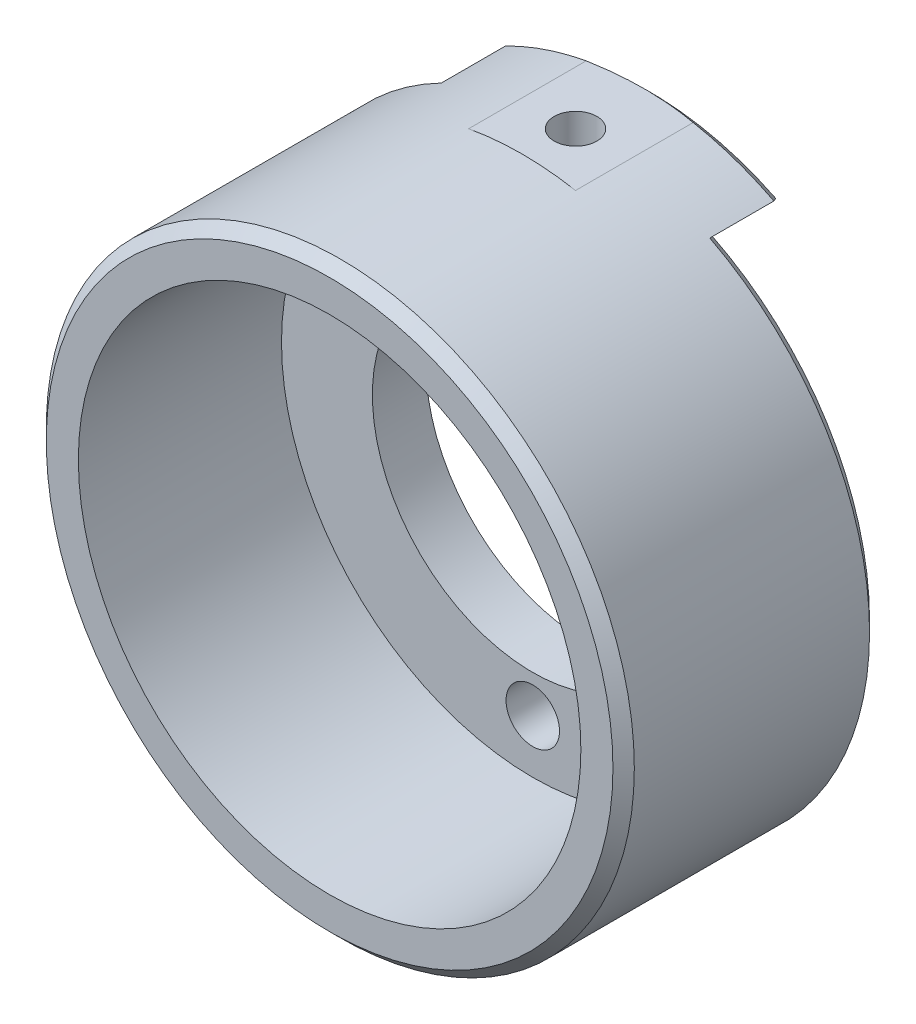
SolidWorks part; units mm, degrees
ref_plane "Front Plane" through (0, 0, 0) normal (0, 0, 1) x (1, 0, 0)
ref_plane "Top Plane" through (0, 0, 0) normal (0, 1, 0) x (1, 0, 0)
ref_plane "Right Plane" through (0, 0, 0) normal (1, 0, 0) x (0, 0, -1)
sketch "Sketch1" plane through (0, 0, 0) normal (0, 1, 0) x (1, 0, 0)
  line L0 (0, -8.6957) -> (0, 15.3043) construction
  line L1 (-15, 24) -> (-23.5, 24)
  line L2 (-15, 24) -> (-15, 19)
  line L3 (-15, 19) -> (-23.5, 19)
  line L4 (-23.5, 24) -> (-23.5, 19)
  line L5 (-23.5, 24) -> (-27.5, 24)
  line L6 (-23.5, 24) -> (-23.5, 0)
  line L7 (-23.5, 0) -> (-27.5, 0)
  line L8 (-27.5, 24) -> (-27.5, 0)
  point P9 (0, 0)
  dimension "D1" = 24
  dimension "D2" = 19
  dimension "D3" = 15
  dimension "D4" = 27.5
  dimension "D5" = 23.5
revolve "Revolve1" add sketch "Sketch1" angle 360 about L0
sketch "Sketch2" plane through (0, 0, -24) normal (0, 0, -1) x (-1, 0, 0)
  line L0 (-2.2498, -15.8188) -> (-12.5556, -24.4665)
  line L1 (2.2498, -15.8188) -> (12.5556, -24.4665)
  line L2 (0, 0) -> (0, -33.4379) construction
  line L3 (0, 0) -> (7.8156, 0) construction
  line L4 (2.2498, 15.8188) -> (12.5556, 24.4665)
  line L5 (-2.2498, 15.8188) -> (-12.5556, 24.4665)
  circle A0 centre (0, -18.5) radius 3.5
  circle A1 centre (0, -18.5) radius 2.5
  circle A2 centre (0, 0) radius 27.5 construction
  circle A3 centre (0, 0) radius 15 construction
  circle A4 centre (0, 18.5) radius 2.5
  circle A5 centre (0, 18.5) radius 3.5
  arc A6 (-12.5556, -24.4665) -> (12.5556, -24.4665) centre (0, 0) ccw
  circle A7 centre (0, 0) radius 27.5
  arc A8 (12.5556, 24.4665) -> (-12.5556, 24.4665) centre (0, 0) ccw
  circle M4 centre (0, 0) radius 27.5
  dimension "D1" = 5
  dimension "D2" = 100
  dimension "D3" = 37
  dimension "D4" = 0
extrude "Boss-Extrude1" add sketch "Sketch2" along normal blind 6 contours L5 A5 L4 M4 | A5 A4 | A0 A1 | A0 L0 L1 M4 region at (0, -23.3823, -24) region at (0, -15.099, -24) region at (0, 23.3823, -24) region at (1.4373, 21.5824, -24)
chamfer "Chamfer1" distance 1 angle 45 5 edges at (27.5, 0, 0) (-27.5, 0, -24) (0, -27.5, -30) (27.5, 0, -24) (0, 27.5, -30)
ref_plane "Plane1" through (0, 30, 0) normal (0, 1, 0) x (1, 0, 0)
sketch "Sketch5" plane through (0, 0, -30) normal (0, 0, -1) x (-1, 0, 0)
  line L0 (5, 27.0416) -> (-5, 27.0416)
  line L1 (0, 0) -> (0, 27.0416) construction
  circle A1 centre (0, 0) radius 27.5
  arc A2 (12.5556, 24.4665) -> (-12.5556, 24.4665) centre (0, 0) ccw construction
  point P3 (0, 25.2007)
  point P7 (0, 0)
  point P11 (0, 0)
  dimension "D1" = 10
sketch "Sketch4" plane through (0, 30, 0) normal (0, 1, 0) x (1, 0, 0)
  line L0 (-5, 30) -> (5, 30)
  line L1 (-5, 30) -> (-5, 18)
  line L2 (-5, 18) -> (5, 18)
  line L3 (5, 30) -> (5, 18)
  line L4 (0, 35) -> (0, 17.3135) construction
  line L5 (11.7216, 30) -> (-11.7216, 30) construction
  circle A0 centre (0, 23) radius 2
  dimension "D3" = 4
  dimension "D1" = 12
  dimension "D2" = 10
  dimension "D4" = 7
extrude "Cut-Extrude1" cut sketch "Sketch4" against normal up to vertex (2.9584 mm away) up to point (-5, 27.0416, -30)
extrude "Cut-Extrude2" cut sketch "Sketch4<3>" against normal offset from surface (7.9584 mm away) 5 contours A0 L4 | L4 A0 region at (0.8488, 30, -23) region at (-0.8488, 30, -23) up to face at (0, 27.0416, -21)
sketch "Sketch4<3>" plane through (0, 30, 0) normal (0, 1, 0) x (1, 0, 0) same geometry as "Sketch4"
mirror "Mirror2" about plane through (0, 0, 0) normal (0, 1, 0) of "Cut-Extrude1"
sketch "Sketch7" plane through (0, 27.0416, 0) normal (0, 1, 0) x (1, 0, 0)
  circle A1 centre (0, 23) radius 2
  circle A2 centre (0, 23) radius 2
  dimension "D1" = 0
sketch "Sketch8" plane through (0, -27.0416, 0) normal (0, -1, 0) x (1, 0, 0)
  circle A1 centre (0, -23) radius 2
  circle A2 centre (0, -23) radius 2
  dimension "D1" = 0
extrude "Cut-Extrude8" cut sketch "Sketch8" against normal offset from surface 5 and the other way blind 5 up to face at (1.25, -27.0416, -23.5)
extrude "Cut-Extrude9" cut sketch "Sketch2<3>" against normal through all contours A1 | A4 | A4 region at (0, -18.5, -24) region at (0, 18.5, -24)
sketch "Sketch2<3>" plane through (0, 0, -24) normal (0, 0, -1) x (-1, 0, 0) same geometry as "Sketch2"
